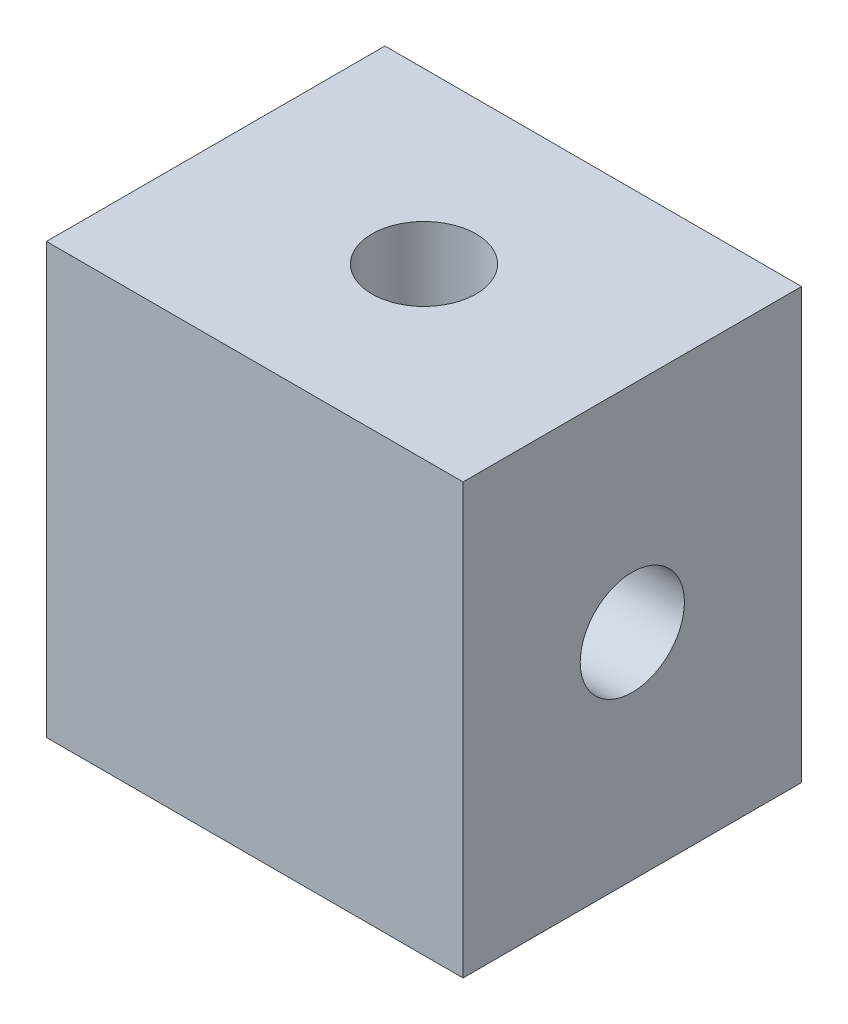
SolidWorks part; units mm, degrees
ref_plane "Front Plane" through (0, 0, 0) normal (0, 0, 1) x (1, 0, 0)
ref_plane "Top Plane" through (0, 0, 0) normal (0, 1, 0) x (1, 0, 0)
ref_plane "Right Plane" through (0, 0, 0) normal (1, 0, 0) x (0, 0, -1)
ref_plane "PL_Block_base" through (0, 0, -13) normal (0, 0, 1) x (1, 0, 0)
sketch "SK_Block" plane through (0, 0, -13) normal (0, 0, 1) x (1, 0, 0)
  line L0 (-16, -16.5) -> (16, -16.5)
  line L1 (16, -16.5) -> (16, 16.5)
  line L2 (16, 16.5) -> (-16, 16.5)
  line L3 (-16, 16.5) -> (-16, -16.5)
  dimension "P1" = 16
  dimension "P2" = 16.5
  dimension "P3" = 16
  dimension "P4" = 16.5
  dimension "P5" = 16
  dimension "P6" = 16.5
  dimension "P7" = 16
  dimension "P8" = 16.5
extrude "Block" add sketch "SK_Block" along normal blind 26
ref_plane "PL_Pitch_Bore_base" through (0, -20, 0) normal (0, 1, 0) x (1, 0, 0)
sketch "SK_Pitch_Bore" plane through (0, -20, 0) normal (0, 1, 0) x (1, 0, 0)
  circle A0 centre (0, 0) radius 4
  dimension "D1_SK_Pitch_Bore" = 8
extrude "Pitch_Bore" cut sketch "SK_Pitch_Bore" along normal blind 40
ref_plane "PL_Roll_Bore_base" through (-20, 0, 0) normal (1, 0, 0) x (0, 0, -1)
sketch "SK_Roll_Bore" plane through (-20, 0, 0) normal (1, 0, 0) x (0, 0, -1)
  circle A0 centre (0, 0) radius 4
  dimension "D1_SK_Roll_Bore" = 8
extrude "Roll_Bore" cut sketch "SK_Roll_Bore" along normal blind 40
equation "\"Cross_size\" = 32"
